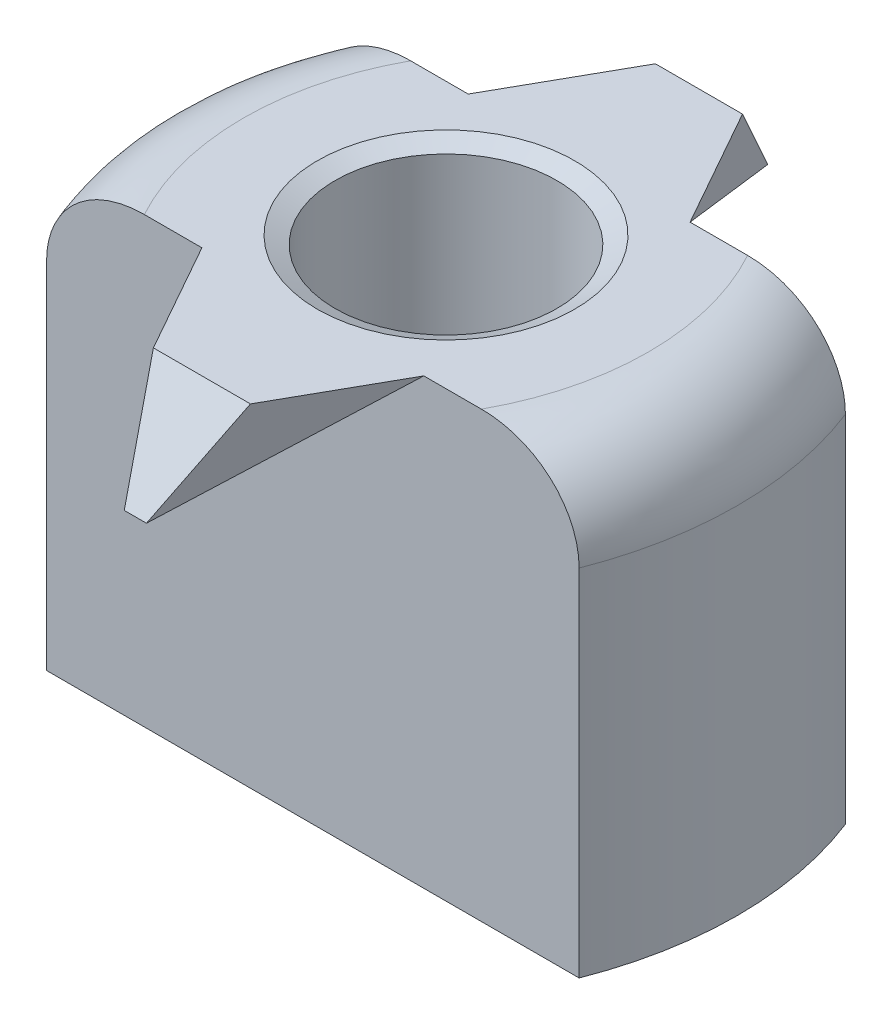
SolidWorks part; units mm, degrees
ref_plane "Alzado" through (0, 0, 0) normal (0, 0, 1) x (1, 0, 0)
ref_plane "Planta" through (0, 0, 0) normal (0, 1, 0) x (1, 0, 0)
ref_plane "Vista lateral" through (0, 0, 0) normal (1, 0, 0) x (0, 0, -1)
sketch "Croquis1" plane through (0, 0, 0) normal (0, 1, 0) x (1, 0, 0)
  line L0 (4.858, -8.38) -> (4.858, -14.38)
  line L1 (-1.142, -14.38) -> (10.858, -14.38)
  line L3 (10.858, -8.38) -> (-1.142, -8.38)
  arc A0 (10.858, -8.38) -> (10.858, -14.38) centre (3.1789, -11.38) cw
  arc A2 (-1.142, -8.38) -> (-1.142, -14.38) centre (6.5371, -11.38) ccw
  dimension "D1" = 6
  dimension "D2" = 12
extrude "Saliente-Extruir1" add sketch "Croquis1" along normal blind 10 contours L3 A2 L1 L0 | A0 L3 L0 L1 region at (8.0499, 0, 11.38) region at (1.6661, 0, 11.38)
sketch "Croquis2" plane through (0, 10, 0) normal (0, 1, 0) x (1, 0, 0)
  circle A0 centre (4.858, -11.38) radius 2.5
extrude "Cortar-Extruir1" cut sketch "Croquis2" against normal blind 10
chamfer "Chaflán1" distance 0.4 angle 25 1 edges at (4.858, 10, 13.88) first distance on face at (4.858, 10, 13.88)
sketch "Croquis3" plane through (0, 10, 0) normal (0, 1, 0) x (1, 0, 0)
  line L0 (4.858, -14.38) -> (4.858, -8.38)
  line L1 (-1.142, -14.38) -> (10.858, -14.38) construction
  line L2 (10.858, -8.38) -> (-1.142, -8.38) construction
  line L3 (4.858, -8.38) -> (4.858, -4.38)
  line L4 (7.358, -8.38) -> (2.358, -8.38)
  line L5 (7.358, -8.38) -> (5.108, -4.38)
  line L6 (5.108, -4.38) -> (4.608, -4.38)
  line L7 (4.608, -4.38) -> (2.358, -8.38)
  point P10 (4.858, -8.38)
  line M5 (10.858, -8.38) -> (-1.142, -8.38)
  dimension "D1" = 0.25
  dimension "D2" = 0.25
extrude "Saliente-Extruir2" add sketch "Croquis3" against normal blind 2 contours L6 L7 L3 M5 | L5 L6 L3 M5 region at (4.0171, 10, 6.9255) region at (5.6989, 10, 6.9255)
sketch "Croquis4" plane through (0, 10, 0) normal (0, 1, 0) x (1, 0, 0)
  line L0 (2.358, -8.38) -> (7.358, -8.38)
  line L1 (4.858, -8.38) -> (4.858, -5.68)
  line L2 (4.858, -5.68) -> (5.8393, -5.68)
  line L3 (7.358, -8.38) -> (5.108, -4.38) construction
  point P9 (0, 0)
sketch "Croquis5" plane through (2.0087, 0, -1.1299) normal (0.8716, 0, -0.4903) x (-0.4903, 0, -0.8716)
  line L0 (-7.8133, 10) -> (-6.3218, 10)
  line L1 (-6.3218, 10) -> (-6.3218, 8)
  line L2 (-6.3218, 8) -> (-7.8133, 10)
extrude "Cortar-Extruir2" cut sketch "Croquis5" along direction (-1, 0, 0) on the side against the normal blind 2
sketch "Croquis8" plane through (0, 8, 0) normal (0, -1, 0) x (1, 0, 0)
  line L0 (5.108, 4.38) -> (5.108, 8.38)
  line L1 (7.358, 8.38) -> (2.358, 8.38) construction
  line L2 (5.108, 8.38) -> (7.358, 8.38)
  line L3 (7.358, 8.38) -> (5.108, 4.38)
sketch "Croquis9" plane through (2.0087, 0, -1.1299) normal (0.8716, 0, -0.4903) x (-0.4903, 0, -0.8716)
  line L0 (-6.3218, 8) -> (-10.9112, 10)
  line L1 (-10.9112, 10) -> (-10.9112, 8)
  line L2 (-10.9112, 8) -> (-10.9112, 10) construction
ref_plane "Plano1" through (-1.7178, 1.9326, 0) normal (0.6644, -0.7474, 0) x (-0.7474, -0.6644, 0)
sketch "Croquis10" plane through (-1.7178, 1.9326, 0) normal (0.6644, -0.7474, 0) x (-0.7474, -0.6644, 0)
  line L0 (-12.1431, -8.38) -> (-9.1327, -8.38)
  line L1 (-9.1327, -8.38) -> (-9.1327, -4.38)
  line L2 (-9.1327, -4.38) -> (-12.1431, -8.38)
extrude "Cortar-Extruir4" cut sketch "Croquis10" along direction (0, -1, 0) on the side of the normal up to vertex (2.3253 mm away) up to point (10.858, 10, 8.38)
sketch "Croquis11" plane through (5.372, 0, 3.0218) normal (-0.8716, 0, -0.4903) x (-0.4903, 0, 0.8716)
  line L0 (1.5584, 8) -> (6.1478, 10)
  line L1 (6.1478, 10) -> (6.1478, 8)
  line L2 (6.1478, 8) -> (1.5584, 8)
sketch "Croquis12" plane through (0, 8, 0) normal (0, -1, 0) x (1, 0, 0)
  line L0 (4.608, 4.38) -> (4.608, 8.38)
  line L1 (5.108, 8.38) -> (2.358, 8.38) construction
  line L2 (4.608, 4.38) -> (2.358, 8.38) construction
  line L3 (4.608, 4.38) -> (2.358, 8.38)
  line L4 (4.608, 4.38) -> (2.358, 8.38)
ref_plane "Plano2" through (6.0063, 6.7571, 0) normal (0.6644, 0.7474, 0) x (0.7474, -0.6644, 0)
sketch "Croquis13" plane through (6.0063, 6.7571, 0) normal (0.6644, 0.7474, 0) x (0.7474, -0.6644, 0)
  line L0 (-1.8708, -8.38) -> (-1.8708, -4.38)
  line L1 (-1.8708, -4.38) -> (-4.8812, -8.38)
  line L2 (-4.8812, -8.38) -> (-1.8708, -8.38)
extrude "Cortar-Extruir5" cut sketch "Croquis13" along direction (0, -1, 0) on the side against the normal blind 4
sketch "Croquis14" plane through (0, 10, 0) normal (0, 1, 0) x (1, 0, 0)
  line L0 (11.4232, -11.38) -> (-1.7072, -11.38)
  arc A0 (10.858, -14.38) -> (10.858, -8.38) centre (3.1789, -11.38) ccw construction
  arc A1 (-1.142, -8.38) -> (-1.142, -14.38) centre (6.5371, -11.38) ccw construction
ref_plane "Plano3" through (0, 0, 11.38) normal (0, 0, -1) x (-1, 0, 0)
mirror "Simetría1" about plane through (0, 0, 11.38) normal (0, 0, -1) of "Saliente-Extruir2"
mirror "Simetría3" about plane through (0, 0, 11.38) normal (0, 0, -1) of "Cortar-Extruir4", "Cortar-Extruir5"
sketch "Croquis15" plane through (0, 10, 0) normal (0, 1, 0) x (1, 0, 0)
  line L0 (7.358, -14.38) -> (2.358, -14.38)
  line L1 (4.858, -14.38) -> (4.858, -16.88)
  line L2 (4.858, -16.88) -> (3.7643, -16.88)
  line L4 (4.608, -18.38) -> (2.358, -14.38) construction
sketch "Croquis16" plane through (-4.3533, 0, 2.4487) normal (-0.8716, 0, 0.4903) x (0.4903, 0, 0.8716)
  line L0 (16.5577, 10) -> (18.2787, 8)
  line L1 (18.2787, 8) -> (18.2787, 10)
  line L2 (18.2787, 10) -> (16.5577, 10)
extrude "Cortar-Extruir6" cut sketch "Croquis16" along direction (-1, 0, 0) on the side against the normal blind 4
fillet "Redondeo1" radius 2 2 edges at (-1.7072, 10, 11.38) (11.4232, 10, 11.38)
